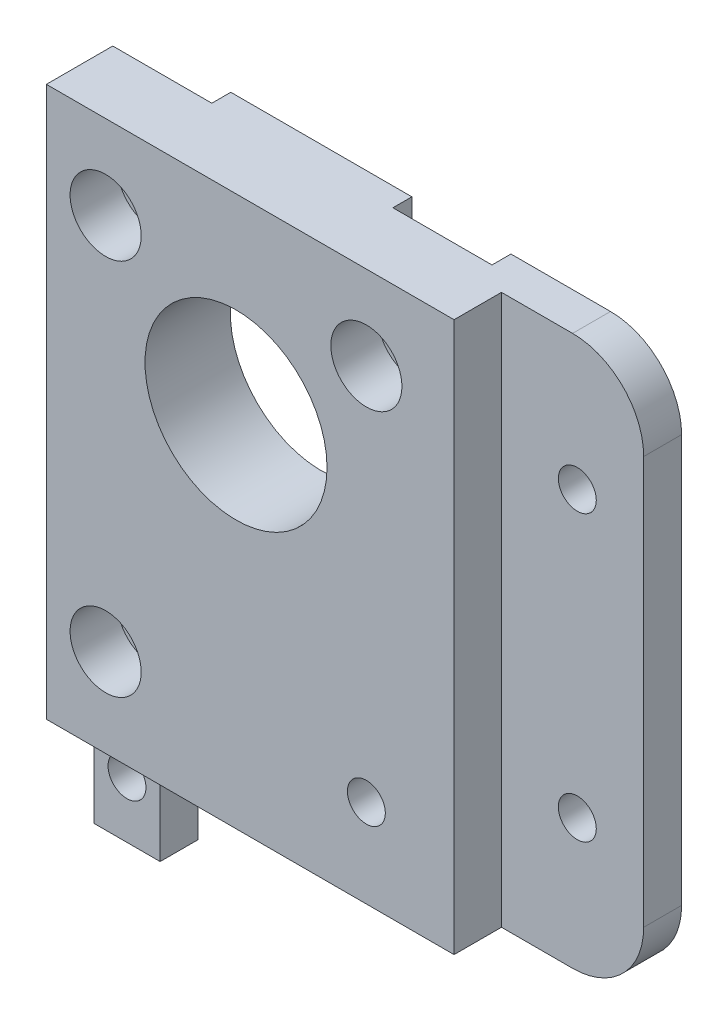
SolidWorks part; units mm, degrees
material "1060 Alloy"
ref_plane "Front Plane" through (0, 0, 0) normal (0, 0, 1) x (1, 0, 0)
ref_plane "Top Plane" through (0, 0, 0) normal (0, 1, 0) x (1, 0, 0)
ref_plane "Right Plane" through (0, 0, 0) normal (1, 0, 0) x (0, 0, -1)
sketch "Sketch1" plane through (0, 0, 0) normal (0, 0, 1) x (1, 0, 0)
  line L0 (-13.75, -19.7) -> (-9.6769, -16.8) construction
  line L3 (20, 29) -> (38, 29)
  line L8 (20, -29) -> (-20, -29)
  line L9 (20, -29) -> (20, 29) construction
  line L10 (38, 29) -> (38, -29)
  line L11 (20, 29) -> (-20, 29)
  line L14 (-20, -29) -> (-20, 29)
  line L15 (20, -29) -> (-20, 29) construction
  line L16 (20, 29) -> (-20, -29) construction
  line L17 (-16.186, -16.2786) -> (-12.1129, -13.3786)
  line L18 (-11.314, -23.1214) -> (-7.2409, -20.2214)
  line L19 (0, -29) -> (0, 29) construction
  line L22 (38, -29) -> (20, -29)
  line L23 (17.2075, -17.3155) -> (20, -21.3647)
  line L24 (9.55, -19.7) -> (9.55, -29)
  line L25 (-9.55, 20.15) -> (-9.55, 29)
  line L26 (-17.2075, 17.7655) -> (-20, 21.8147)
  line L27 (9.55, 20.15) -> (9.55, 29)
  line L28 (17.2075, 17.7655) -> (20, 21.8147)
  line L29 (20, 21.8147) -> (20, 29)
  line L30 (-16.186, -16.2786) -> (-20, -16.2786)
  line L31 (20, -29) -> (20, -21.3647)
  line L32 (-20, -23.9) -> (-13.75, -23.9)
  circle A18 centre (-13.75, 20.15) radius 4.2
  circle A19 centre (13.75, 20.15) radius 4.2
  circle A20 centre (13.75, -19.7) radius 4.2
  arc A21 (-16.186, -16.2786) -> (-11.314, -23.1214) centre (-13.75, -19.7) ccw
  arc A22 (-7.2409, -20.2214) -> (-12.1129, -13.3786) centre (-9.6769, -16.8) ccw
  circle A23 centre (0, 8.8) radius 9.6
  circle A24 centre (-5.725, -6.1) radius 4.2
  circle A25 centre (5.725, -6.1) radius 4.2
  point P0 (0, 0)
  point P14 (-6.2555, -14.364)
  point P31 (-11.7135, -18.25)
  point P37 (5.725, -10.3)
  point P43 (20, 29)
  point P45 (-15.0434, -29)
  point P46 (-20, 29)
  point P47 (-11.314, -23.1214)
  point P48 (-16.186, -29)
  point P49 (-20, -23.9286)
  point P50 (-13.75, -23.9)
  point P51 (-20, -23.9)
  point P52 (-20, -33.3506)
  point P54 (-12.5652, -23.7294)
  point P55 (-20, -23.9)
  dimension "D1" = 58
  dimension "D2" = 40
  dimension "D3" = 12.2
  dimension "D4" = 8.4
  dimension "D5" = 8.4
  dimension "D6" = 19.2
  dimension "D7" = 9.3
  dimension "D8" = 27.5
  dimension "D9" = 39.85
  dimension "D10" = 5
  dimension "D12" = 20.2
  dimension "D13" = 11.45
  dimension "D14" = 22.9
  dimension "D15" = 18
extrude "Boss-Extrude1" add sketch "Sketch1" along normal blind 2 contours L11 L14 L8 L9 A25 A24 A23 A22 L18 A21 L17 A20 A19 A18 region at (12.0942, -0.9505, 0)
sketch "Sketch4" plane through (0, 0, 2) normal (0, 0, 1) x (1, 0, 0)
  line L0 (0, -29) -> (0, 29) construction
  line L6 (38, -29) -> (20, -29) construction
  line L8 (-20, -29) -> (38, -29)
  line L11 (38, -29) -> (38, 29)
  line L12 (-20, 29) -> (-20, -29)
  line L13 (-20, -16.2786) -> (-20, 21.8147) construction
  line L14 (-20, 29) -> (38, 29)
  line L15 (20, 29) -> (38, 29) construction
  line L16 (38, 29) -> (38, -29) construction
  circle A2 centre (13.75, -19.7) radius 2
  circle A3 centre (-13.75, 20.15) radius 2
  circle A4 centre (13.75, 20.15) radius 2
  circle A10 centre (-13.75, -19.7) radius 2
  circle A11 centre (0, 8.8) radius 9.6
  circle A12 centre (0, 8.8) radius 9.6 construction
  dimension "D1" = 4
extrude "Boss-Extrude3" add sketch "Sketch4" along normal blind 2
sketch "Sketch5" plane through (0, 0, 4) normal (0, 0, 1) x (1, 0, 0)
  line L0 (-20, 0) -> (38, 0) construction
  line L3 (-20, 29) -> (-20, -29) construction
  line L4 (38, -29) -> (38, 29) construction
  circle A0 centre (31, 15) radius 2
  circle A1 centre (31, -15) radius 2
  dimension "D1" = 4
  dimension "D2" = 15
  dimension "D3" = 51
extrude "Cut-Extrude1" cut sketch "Sketch5" against normal blind 4
ref_plane "Plane1" through (0, 0, 0) normal (0, 0, -1) x (-1, 0, 0)
sketch "Sketch6" plane through (0, 0, 4) normal (0, 0, 1) x (1, 0, 0)
  line L0 (23, 29) -> (23, -29)
  line L1 (38, 29) -> (-20, 29) construction
  line L2 (-20, -29) -> (38, -29) construction
  line L3 (38, -29) -> (38, 29) construction
  circle A52 centre (-13.75, 20.15) radius 3.75
  circle A53 centre (13.75, 20.15) radius 3.75
  circle A54 centre (31, 15) radius 2
  circle A55 centre (13.75, -19.7) radius 3.75
  circle A56 centre (-13.75, -19.7) radius 3.75
  circle A57 centre (31, -15) radius 2
  circle A59 centre (31, 15) radius 2 construction
  circle A60 centre (31, -15) radius 2 construction
  point P24 (-16.2151, -34.8284)
  point P30 (0, 0)
  line M5 (-20, 29) -> (-20, -29)
  line M6 (-20, -29) -> (38, -29)
  line M7 (38, -29) -> (38, 29)
  line M8 (38, 29) -> (-20, 29)
  circle M9 centre (13.75, -19.7) radius 2
  circle M11 centre (0, 8.8) radius 9.6
  dimension "D1" = 7.5
  dimension "D2" = 15
extrude "Boss-Extrude4" add sketch "Sketch6" along normal blind 5 contours A57 A56 A55 A54 A53 A52 M8 M5 M6 M7 M11 | A55 M9 region at (1.8449, -1.2761, 4) region at (10.1061, -19.7, 4)
sketch "Sketch7" plane through (0, 0, 4) normal (0, 0, 1) x (1, 0, 0)
  line L0 (38, -29) -> (38, 29) construction
  line L1 (30.5, 29) -> (38, 29)
  line L2 (38, 29) -> (38, 21.5)
  line L3 (-20, 0) -> (38, 0) construction
  line L4 (-20, 29) -> (-20, -29) construction
  line L5 (38, -29) -> (38, -21.5)
  line L6 (30.5, -29) -> (38, -29)
  arc A0 (38, 21.5) -> (30.5, 29) centre (30.5, 21.5) ccw
  arc A1 (38, -21.5) -> (30.5, -29) centre (30.5, -21.5) cw
  dimension "D1" = 15
extrude "Cut-Extrude2" cut sketch "Sketch7" against normal through all
sketch "Sketch9" plane through (0, 0, 4) normal (0, 0, 1) x (1, 0, 0)
  line L0 (-20, -29) -> (-20, -41)
  line L1 (-20, -41) -> (-13, -41)
  line L2 (-13, -41) -> (-13, -29)
  line L3 (-20, -29) -> (23, -29) construction
  line L4 (-13, -29) -> (-20, -29)
  circle A0 centre (-16.5, -35) radius 2
  point P14 (-20, -35)
  point P15 (-16.5, -41)
  dimension "D3" = 4
  dimension "D1" = 12
  dimension "D2" = 7
extrude "Boss-Extrude6" add sketch "Sketch9" against normal through all
